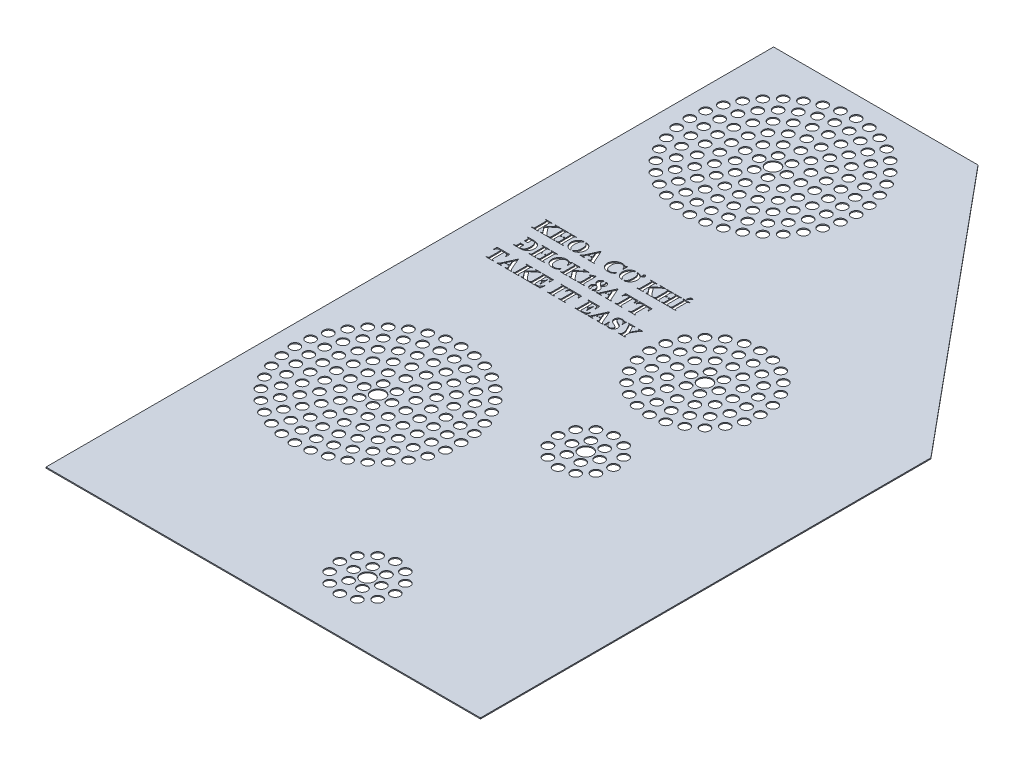
SolidWorks part; units mm, degrees
ref_plane "Front Plane" through (0, 0, 0) normal (0, 0, 1) x (1, 0, 0)
ref_plane "Top Plane" through (0, 0, 0) normal (0, 1, 0) x (1, 0, 0)
ref_plane "Right Plane" through (0, 0, 0) normal (1, 0, 0) x (0, 0, -1)
sketch "Sketch1" plane through (0, 0, 0) normal (0, 1, 0) x (1, 0, 0)
  line L0 (313.5, 0) -> (-313.5, 0)
  line L1 (-313.5, 0) -> (-313.5, 1050)
  line L2 (-313.5, 1050) -> (-18.5, 1050)
  line L3 (-18.5, 1050) -> (313.5, 650)
  line L4 (313.5, 650) -> (313.5, 0)
  line L5 (-263.5, 650) -> (-63.5, 650) construction
  circle A2 centre (-144.5, 330.2) radius 7
  circle A3 centre (-124.5, 330.2) radius 7
  circle A4 centre (-104.5, 330.2) radius 7
  circle A5 centre (-84.5, 330.2) radius 7
  circle A6 centre (-64.5, 330.2) radius 7
  circle A7 centre (-44.5, 330.2) radius 7
  circle A8 centre (-154.5, 312.8795) radius 7
  circle A9 centre (-174.5, 312.8795) radius 7
  circle A10 centre (-184.5, 330.2) radius 7
  circle A11 centre (-174.5, 347.5205) radius 7
  circle A12 centre (-154.5, 347.5205) radius 7
  circle A13 centre (-129.859, 310.2) radius 7
  circle A14 centre (-144.5, 295.559) radius 7
  circle A15 centre (-164.5, 290.2) radius 7
  circle A16 centre (-184.5, 295.559) radius 7
  circle A17 centre (-199.141, 310.2) radius 7
  circle A18 centre (-204.5, 330.2) radius 7
  circle A19 centre (-199.141, 350.2) radius 7
  circle A20 centre (-184.5, 364.841) radius 7
  circle A21 centre (-164.5, 370.2) radius 7
  circle A22 centre (-144.5, 364.841) radius 7
  circle A23 centre (-129.859, 350.2) radius 7
  circle A24 centre (-108.1184, 309.6788) radius 7
  circle A25 centre (-118.5373, 291.6327) radius 7
  circle A26 centre (-134.5, 278.2385) radius 7
  circle A27 centre (-154.0811, 271.1115) radius 7
  circle A28 centre (-174.9189, 271.1115) radius 7
  circle A29 centre (-194.5, 278.2385) radius 7
  circle A30 centre (-210.4627, 291.6327) radius 7
  circle A31 centre (-220.8816, 309.6788) radius 7
  circle A32 centre (-224.5, 330.2) radius 7
  circle A33 centre (-220.8816, 350.7212) radius 7
  circle A34 centre (-210.4627, 368.7673) radius 7
  circle A35 centre (-194.5, 382.1615) radius 7
  circle A36 centre (-174.9189, 389.2885) radius 7
  circle A37 centre (-154.0811, 389.2885) radius 7
  circle A38 centre (-134.5, 382.1615) radius 7
  circle A39 centre (-118.5373, 368.7673) radius 7
  circle A40 centre (-108.1184, 350.7212) radius 7
  circle A41 centre (-87.2259, 309.4945) radius 7
  circle A42 centre (-95.218, 290.2) radius 7
  circle A43 centre (-107.9315, 273.6315) radius 7
  circle A44 centre (-124.5, 260.918) radius 7
  circle A45 centre (-143.7945, 252.9259) radius 7
  circle A46 centre (-164.5, 250.2) radius 7
  circle A47 centre (-185.2055, 252.9259) radius 7
  circle A48 centre (-204.5, 260.918) radius 7
  circle A49 centre (-221.0685, 273.6315) radius 7
  circle A50 centre (-233.782, 290.2) radius 7
  circle A51 centre (-241.7741, 309.4945) radius 7
  circle A52 centre (-244.5, 330.2) radius 7
  circle A53 centre (-241.7741, 350.9055) radius 7
  circle A54 centre (-233.782, 370.2) radius 7
  circle A55 centre (-221.0685, 386.7685) radius 7
  circle A56 centre (-204.5, 399.482) radius 7
  circle A57 centre (-185.2055, 407.4741) radius 7
  circle A58 centre (-164.5, 410.2) radius 7
  circle A59 centre (-143.7945, 407.4741) radius 7
  circle A60 centre (-124.5, 399.482) radius 7
  circle A61 centre (-107.9315, 386.7685) radius 7
  circle A62 centre (-95.218, 370.2) radius 7
  circle A63 centre (-87.2259, 350.9055) radius 7
  circle A64 centre (-66.6852, 309.4088) radius 7
  circle A65 centre (-73.1455, 289.5263) radius 7
  circle A66 centre (-83.5983, 271.4215) radius 7
  circle A67 centre (-97.5869, 255.8855) radius 7
  circle A68 centre (-114.5, 243.5975) radius 7
  circle A69 centre (-133.5983, 235.0943) radius 7
  circle A70 centre (-154.0472, 230.7478) radius 7
  circle A71 centre (-174.9528, 230.7478) radius 7
  circle A72 centre (-195.4017, 235.0943) radius 7
  circle A73 centre (-214.5, 243.5975) radius 7
  circle A74 centre (-231.4131, 255.8855) radius 7
  circle A75 centre (-245.4017, 271.4215) radius 7
  circle A76 centre (-255.8545, 289.5263) radius 7
  circle A77 centre (-262.3148, 309.4088) radius 7
  circle A78 centre (-264.5, 330.2) radius 7
  circle A79 centre (-262.3148, 350.9912) radius 7
  circle A80 centre (-255.8545, 370.8737) radius 7
  circle A81 centre (-245.4017, 388.9785) radius 7
  circle A82 centre (-231.4131, 404.5145) radius 7
  circle A83 centre (-214.5, 416.8025) radius 7
  circle A84 centre (-195.4017, 425.3057) radius 7
  circle A85 centre (-174.9528, 429.6522) radius 7
  circle A86 centre (-154.0472, 429.6522) radius 7
  circle A87 centre (-133.5983, 425.3057) radius 7
  circle A88 centre (-114.5, 416.8025) radius 7
  circle A89 centre (-97.5869, 404.5145) radius 7
  circle A90 centre (-83.5983, 388.9785) radius 7
  circle A91 centre (-73.1455, 370.8737) radius 7
  circle A92 centre (-66.6852, 350.9912) radius 7
  circle A93 centre (-46.3231, 309.3622) radius 7
  circle A94 centre (-51.7369, 289.1576) radius 7
  circle A95 centre (-60.577, 270.2) radius 7
  circle A96 centre (-72.5747, 253.0655) radius 7
  circle A97 centre (-87.3655, 238.2747) radius 7
  circle A98 centre (-104.5, 226.277) radius 7
  circle A99 centre (-123.4576, 217.4369) radius 7
  circle A100 centre (-143.6622, 212.0231) radius 7
  circle A101 centre (-164.5, 210.2) radius 7
  circle A102 centre (-185.3378, 212.0231) radius 7
  circle A103 centre (-205.5424, 217.4369) radius 7
  circle A104 centre (-224.5, 226.277) radius 7
  circle A105 centre (-241.6345, 238.2747) radius 7
  circle A106 centre (-256.4253, 253.0655) radius 7
  circle A107 centre (-268.423, 270.2) radius 7
  circle A108 centre (-277.2631, 289.1576) radius 7
  circle A109 centre (-282.6769, 309.3622) radius 7
  circle A110 centre (-284.5, 330.2) radius 7
  circle A111 centre (-282.6769, 351.0378) radius 7
  circle A112 centre (-277.2631, 371.2424) radius 7
  circle A113 centre (-268.423, 390.2) radius 7
  circle A114 centre (-256.4253, 407.3345) radius 7
  circle A115 centre (-241.6345, 422.1253) radius 7
  circle A116 centre (-224.5, 434.123) radius 7
  circle A117 centre (-205.5424, 442.9631) radius 7
  circle A118 centre (-185.3378, 448.3769) radius 7
  circle A119 centre (-164.5, 450.2) radius 7
  circle A120 centre (-143.6622, 448.3769) radius 7
  circle A121 centre (-123.4576, 442.9631) radius 7
  circle A122 centre (-104.5, 434.123) radius 7
  circle A123 centre (-87.3655, 422.1253) radius 7
  circle A124 centre (-72.5747, 407.3345) radius 7
  circle A125 centre (-60.577, 390.2) radius 7
  circle A126 centre (-51.7369, 371.2424) radius 7
  circle A127 centre (-46.3231, 351.0378) radius 7
  circle A129 centre (-144.5, 900.2) radius 7
  circle A130 centre (-124.5, 900.2) radius 7
  circle A131 centre (-104.5, 900.2) radius 7
  circle A132 centre (-84.5, 900.2) radius 7
  circle A133 centre (-64.5, 900.2) radius 7
  circle A134 centre (-44.5, 900.2) radius 7
  circle A135 centre (-154.5, 882.8795) radius 7
  circle A136 centre (-174.5, 882.8795) radius 7
  circle A137 centre (-184.5, 900.2) radius 7
  circle A138 centre (-174.5, 917.5205) radius 7
  circle A139 centre (-154.5, 917.5205) radius 7
  circle A140 centre (-129.859, 880.2) radius 7
  circle A141 centre (-144.5, 865.559) radius 7
  circle A142 centre (-164.5, 860.2) radius 7
  circle A143 centre (-184.5, 865.559) radius 7
  circle A144 centre (-199.141, 880.2) radius 7
  circle A145 centre (-204.5, 900.2) radius 7
  circle A146 centre (-199.141, 920.2) radius 7
  circle A147 centre (-184.5, 934.841) radius 7
  circle A148 centre (-164.5, 940.2) radius 7
  circle A149 centre (-144.5, 934.841) radius 7
  circle A150 centre (-129.859, 920.2) radius 7
  circle A151 centre (-108.1184, 879.6788) radius 7
  circle A152 centre (-118.5373, 861.6327) radius 7
  circle A153 centre (-134.5, 848.2385) radius 7
  circle A154 centre (-154.0811, 841.1115) radius 7
  circle A155 centre (-174.9189, 841.1115) radius 7
  circle A156 centre (-194.5, 848.2385) radius 7
  circle A157 centre (-210.4627, 861.6327) radius 7
  circle A158 centre (-220.8816, 879.6788) radius 7
  circle A159 centre (-224.5, 900.2) radius 7
  circle A160 centre (-220.8816, 920.7212) radius 7
  circle A161 centre (-210.4627, 938.7673) radius 7
  circle A162 centre (-194.5, 952.1615) radius 7
  circle A163 centre (-174.9189, 959.2885) radius 7
  circle A164 centre (-154.0811, 959.2885) radius 7
  circle A165 centre (-134.5, 952.1615) radius 7
  circle A166 centre (-118.5373, 938.7673) radius 7
  circle A167 centre (-108.1184, 920.7212) radius 7
  circle A168 centre (-87.2259, 879.4945) radius 7
  circle A169 centre (-95.218, 860.2) radius 7
  circle A170 centre (-107.9315, 843.6315) radius 7
  circle A171 centre (-124.5, 830.918) radius 7
  circle A172 centre (-143.7945, 822.9259) radius 7
  circle A173 centre (-164.5, 820.2) radius 7
  circle A174 centre (-185.2055, 822.9259) radius 7
  circle A175 centre (-204.5, 830.918) radius 7
  circle A176 centre (-221.0685, 843.6315) radius 7
  circle A177 centre (-233.782, 860.2) radius 7
  circle A178 centre (-241.7741, 879.4945) radius 7
  circle A179 centre (-244.5, 900.2) radius 7
  circle A180 centre (-241.7741, 920.9055) radius 7
  circle A181 centre (-233.782, 940.2) radius 7
  circle A182 centre (-221.0685, 956.7685) radius 7
  circle A183 centre (-204.5, 969.482) radius 7
  circle A184 centre (-185.2055, 977.4741) radius 7
  circle A185 centre (-164.5, 980.2) radius 7
  circle A186 centre (-143.7945, 977.4741) radius 7
  circle A187 centre (-124.5, 969.482) radius 7
  circle A188 centre (-107.9315, 956.7685) radius 7
  circle A189 centre (-95.218, 940.2) radius 7
  circle A190 centre (-87.2259, 920.9055) radius 7
  circle A191 centre (-66.6852, 879.4088) radius 7
  circle A192 centre (-73.1455, 859.5263) radius 7
  circle A193 centre (-83.5983, 841.4215) radius 7
  circle A194 centre (-97.5869, 825.8855) radius 7
  circle A195 centre (-114.5, 813.5975) radius 7
  circle A196 centre (-133.5983, 805.0943) radius 7
  circle A197 centre (-154.0472, 800.7478) radius 7
  circle A198 centre (-174.9528, 800.7478) radius 7
  circle A199 centre (-195.4017, 805.0943) radius 7
  circle A200 centre (-214.5, 813.5975) radius 7
  circle A201 centre (-231.4131, 825.8855) radius 7
  circle A202 centre (-245.4017, 841.4215) radius 7
  circle A203 centre (-255.8545, 859.5263) radius 7
  circle A204 centre (-262.3148, 879.4088) radius 7
  circle A205 centre (-264.5, 900.2) radius 7
  circle A206 centre (-262.3148, 920.9912) radius 7
  circle A207 centre (-255.8545, 940.8737) radius 7
  circle A208 centre (-245.4017, 958.9785) radius 7
  circle A209 centre (-231.4131, 974.5145) radius 7
  circle A210 centre (-214.5, 986.8025) radius 7
  circle A211 centre (-195.4017, 995.3057) radius 7
  circle A212 centre (-174.9528, 999.6522) radius 7
  circle A213 centre (-154.0472, 999.6522) radius 7
  circle A214 centre (-133.5983, 995.3057) radius 7
  circle A215 centre (-114.5, 986.8025) radius 7
  circle A216 centre (-97.5869, 974.5145) radius 7
  circle A217 centre (-83.5983, 958.9785) radius 7
  circle A218 centre (-73.1455, 940.8737) radius 7
  circle A219 centre (-66.6852, 920.9912) radius 7
  circle A220 centre (-46.3231, 879.3622) radius 7
  circle A221 centre (-51.7369, 859.1576) radius 7
  circle A222 centre (-60.577, 840.2) radius 7
  circle A223 centre (-72.5747, 823.0655) radius 7
  circle A224 centre (-87.3655, 808.2747) radius 7
  circle A225 centre (-104.5, 796.277) radius 7
  circle A226 centre (-123.4576, 787.4369) radius 7
  circle A227 centre (-143.6622, 782.0231) radius 7
  circle A228 centre (-164.5, 780.2) radius 7
  circle A229 centre (-185.3378, 782.0231) radius 7
  circle A230 centre (-205.5424, 787.4369) radius 7
  circle A231 centre (-224.5, 796.277) radius 7
  circle A232 centre (-241.6345, 808.2747) radius 7
  circle A233 centre (-256.4253, 823.0655) radius 7
  circle A234 centre (-268.423, 840.2) radius 7
  circle A235 centre (-277.2631, 859.1576) radius 7
  circle A236 centre (-282.6769, 879.3622) radius 7
  circle A237 centre (-284.5, 900.2) radius 7
  circle A238 centre (-282.6769, 921.0378) radius 7
  circle A239 centre (-277.2631, 941.2424) radius 7
  circle A240 centre (-268.423, 960.2) radius 7
  circle A241 centre (-256.4253, 977.3345) radius 7
  circle A242 centre (-241.6345, 992.1253) radius 7
  circle A243 centre (-224.5, 1004.123) radius 7
  circle A244 centre (-205.5424, 1012.9631) radius 7
  circle A245 centre (-185.3378, 1018.3769) radius 7
  circle A246 centre (-164.5, 1020.2) radius 7
  circle A247 centre (-143.6622, 1018.3769) radius 7
  circle A248 centre (-123.4576, 1012.9631) radius 7
  circle A249 centre (-104.5, 1004.123) radius 7
  circle A250 centre (-87.3655, 992.1253) radius 7
  circle A251 centre (-72.5747, 977.3345) radius 7
  circle A252 centre (-60.577, 960.2) radius 7
  circle A253 centre (-51.7369, 941.2424) radius 7
  circle A254 centre (-46.3231, 921.0378) radius 7
  circle A256 centre (-164.5, 330.2) radius 10
  circle A257 centre (-164.5, 900.2) radius 10
  circle A259 centre (76.5, 581) radius 7
  circle A260 centre (96.5, 581) radius 7
  circle A261 centre (116.5, 581) radius 7
  circle A262 centre (136.5, 581) radius 7
  circle A263 centre (56.5, 581) radius 10
  circle A264 centre (66.5, 563.6795) radius 7
  circle A265 centre (46.5, 563.6795) radius 7
  circle A266 centre (36.5, 581) radius 7
  circle A267 centre (46.5, 598.3205) radius 7
  circle A268 centre (66.5, 598.3205) radius 7
  circle A269 centre (91.141, 561) radius 7
  circle A270 centre (76.5, 546.359) radius 7
  circle A271 centre (56.5, 541) radius 7
  circle A272 centre (36.5, 546.359) radius 7
  circle A273 centre (21.859, 561) radius 7
  circle A274 centre (16.5, 581) radius 7
  circle A275 centre (21.859, 601) radius 7
  circle A276 centre (36.5, 615.641) radius 7
  circle A277 centre (56.5, 621) radius 7
  circle A278 centre (76.5, 615.641) radius 7
  circle A279 centre (91.141, 601) radius 7
  circle A280 centre (112.8816, 560.4788) radius 7
  circle A281 centre (102.4627, 542.4327) radius 7
  circle A282 centre (86.5, 529.0385) radius 7
  circle A283 centre (66.9189, 521.9115) radius 7
  circle A284 centre (46.0811, 521.9115) radius 7
  circle A285 centre (26.5, 529.0385) radius 7
  circle A286 centre (10.5373, 542.4327) radius 7
  circle A287 centre (0.1184, 560.4788) radius 7
  circle A288 centre (-3.5, 581) radius 7
  circle A289 centre (0.1184, 601.5212) radius 7
  circle A290 centre (10.5373, 619.5673) radius 7
  circle A291 centre (26.5, 632.9615) radius 7
  circle A292 centre (46.0811, 640.0885) radius 7
  circle A293 centre (66.9189, 640.0885) radius 7
  circle A294 centre (86.5, 632.9615) radius 7
  circle A295 centre (102.4627, 619.5673) radius 7
  circle A296 centre (112.8816, 601.5212) radius 7
  circle A297 centre (133.7741, 560.2945) radius 7
  circle A298 centre (125.782, 541) radius 7
  circle A299 centre (113.0685, 524.4315) radius 7
  circle A300 centre (96.5, 511.718) radius 7
  circle A301 centre (77.2055, 503.7259) radius 7
  circle A302 centre (56.5, 501) radius 7
  circle A303 centre (35.7945, 503.7259) radius 7
  circle A304 centre (16.5, 511.718) radius 7
  circle A305 centre (-0.0685, 524.4315) radius 7
  circle A306 centre (-12.782, 541) radius 7
  circle A307 centre (-20.7741, 560.2945) radius 7
  circle A308 centre (-23.5, 581) radius 7
  circle A309 centre (-20.7741, 601.7055) radius 7
  circle A310 centre (-12.782, 621) radius 7
  circle A311 centre (-0.0685, 637.5685) radius 7
  circle A312 centre (16.5, 650.282) radius 7
  circle A313 centre (35.7945, 658.2741) radius 7
  circle A314 centre (56.5, 661) radius 7
  circle A315 centre (77.2055, 658.2741) radius 7
  circle A316 centre (96.5, 650.282) radius 7
  circle A317 centre (113.0685, 637.5685) radius 7
  circle A318 centre (125.782, 621) radius 7
  circle A319 centre (133.7741, 601.7055) radius 7
  circle A362 centre (76.5, 409) radius 7
  circle A363 centre (96.5, 409) radius 7
  circle A364 centre (66.5, 391.6795) radius 7
  circle A365 centre (46.5, 391.6795) radius 7
  circle A366 centre (36.5, 409) radius 7
  circle A367 centre (46.5, 426.3205) radius 7
  circle A368 centre (66.5, 426.3205) radius 7
  circle A369 centre (91.141, 389) radius 7
  circle A370 centre (76.5, 374.359) radius 7
  circle A371 centre (56.5, 369) radius 7
  circle A372 centre (36.5, 374.359) radius 7
  circle A373 centre (21.859, 389) radius 7
  circle A374 centre (16.5, 409) radius 7
  circle A375 centre (21.859, 429) radius 7
  circle A376 centre (36.5, 443.641) radius 7
  circle A377 centre (56.5, 449) radius 7
  circle A378 centre (76.5, 443.641) radius 7
  circle A379 centre (91.141, 429) radius 7
  circle A380 centre (56.5, 409) radius 10
  circle A381 centre (76.5, 94) radius 7
  circle A382 centre (96.5, 94) radius 7
  circle A383 centre (66.5, 76.6795) radius 7
  circle A384 centre (46.5, 76.6795) radius 7
  circle A385 centre (36.5, 94) radius 7
  circle A386 centre (46.5, 111.3205) radius 7
  circle A387 centre (66.5, 111.3205) radius 7
  circle A388 centre (91.141, 74) radius 7
  circle A389 centre (76.5, 59.359) radius 7
  circle A390 centre (56.5, 54) radius 7
  circle A391 centre (36.5, 59.359) radius 7
  circle A392 centre (21.859, 74) radius 7
  circle A393 centre (16.5, 94) radius 7
  circle A394 centre (21.859, 114) radius 7
  circle A395 centre (36.5, 128.641) radius 7
  circle A396 centre (56.5, 134) radius 7
  circle A397 centre (76.5, 128.641) radius 7
  circle A398 centre (91.141, 114) radius 7
  circle A399 centre (56.5, 94) radius 10
  text T0 "<b>KHOA CƠ KHÍ</b>\r\n<b>DHCK18ATT</b>\r\n<b>TAKE IT EASY</b>" font "Times New Roman" height 20
  point P35 (-164.5, 330.2)
  point P58 (-164.5, 330.2)
  point P93 (-164.5, 330.2)
  point P139 (-164.5, 330.2)
  point P199 (-164.5, 330.2)
  point P270 (-164.5, 330.2)
  point P294 (-164.5, 900.2)
  point P317 (-164.5, 900.2)
  point P352 (-164.5, 900.2)
  point P398 (-164.5, 900.2)
  point P457 (-164.5, 900.2)
  point P528 (-164.5, 900.2)
  point P550 (56.5, 581)
  point P574 (56.5, 581)
  point P609 (56.5, 581)
  point P656 (56.5, 581)
  point P672 (56.5, 409)
  point P695 (56.5, 409)
  point P710 (56.5, 94)
  point P733 (56.5, 94)
  dimension "D5" = 2
  dimension "D6" = 20
  dimension "D7" = 2
  dimension "D8" = 20
  dimension "D16" = 172
  dimension "D9" = 20
  dimension "D17" = 20
  dimension "D18" = 6
  dimension "D1" = 650
  dimension "D2" = 1050
  dimension "D3" = 627
  dimension "D4" = 295
  dimension "D24" = 370
  dimension "D25" = 469
  dimension "D22" = 200
  dimension "D23" = 50
  dimension "D26" = 400
  dimension "D10" = 6
  dimension "D11" = 12
  dimension "D12" = 18
  dimension "D13" = 24
  dimension "D14" = 30
  dimension "D15" = 36
  dimension "D19" = 12
  dimension "D20" = 18
  dimension "D21" = 24
extrude "Boss-Extrude1" add sketch "Sketch1" along normal blind 1.5
sketch "Sketch2" plane through (0, 1.5, 0) normal (0, 1, 0) x (1, 0, 0)
  line L1 (-227.3073, 658.93) -> (-229.6927, 658.93)
  line L2 (-227.3073, 658.93) -> (-227.3073, 661.988)
  line L3 (-227.3073, 661.988) -> (-229.6927, 661.988)
  line L4 (-229.6927, 658.93) -> (-229.6927, 661.988)
  line L5 (-227.3073, 658.93) -> (-229.6927, 661.988) construction
  line L6 (-227.3073, 661.988) -> (-229.6927, 658.93) construction
  line L7 (-203.7646, 667.9852) -> (-206.7139, 667.9852)
  line L8 (-203.7646, 667.9852) -> (-203.7646, 671.1874)
  line L9 (-203.7646, 671.1874) -> (-206.7139, 671.1874)
  line L10 (-206.7139, 667.9852) -> (-206.7139, 671.1874)
  line L11 (-203.7646, 667.9852) -> (-206.7139, 671.1874) construction
  line L12 (-203.7646, 671.1874) -> (-206.7139, 667.9852) construction
  line L13 (-203.7646, 648.6458) -> (-206.7139, 648.6458)
  line L14 (-203.7646, 648.6458) -> (-203.7646, 652.0165)
  line L15 (-203.7646, 652.0165) -> (-206.7139, 652.0165)
  line L16 (-206.7139, 648.6458) -> (-206.7139, 652.0165)
  line L17 (-203.7646, 648.6458) -> (-206.7139, 652.0165) construction
  line L18 (-203.7646, 652.0165) -> (-206.7139, 648.6458) construction
  line L19 (-183.2916, 655.0807) -> (-185.2189, 655.0807)
  line L20 (-183.2916, 655.0807) -> (-183.2916, 657.4898)
  line L21 (-183.2916, 657.4898) -> (-185.2189, 657.4898)
  line L22 (-185.2189, 655.0807) -> (-185.2189, 657.4898)
  line L23 (-183.2916, 655.0807) -> (-185.2189, 657.4898) construction
  line L24 (-183.2916, 657.4898) -> (-185.2189, 655.0807) construction
  line L25 (-129.4086, 667.9852) -> (-132.6017, 667.9852)
  line L26 (-129.4086, 667.9852) -> (-129.4086, 671.1874)
  line L27 (-129.4086, 671.1874) -> (-132.6017, 671.1874)
  line L28 (-132.6017, 667.9852) -> (-132.6017, 671.1874)
  line L29 (-129.4086, 667.9852) -> (-132.6017, 671.1874) construction
  line L30 (-129.4086, 671.1874) -> (-132.6017, 667.9852) construction
  line L31 (-129.4086, 648.6458) -> (-132.6017, 648.6458)
  line L32 (-129.4086, 648.6458) -> (-129.4086, 652.0165)
  line L33 (-129.4086, 652.0165) -> (-132.6017, 652.0165)
  line L34 (-132.6017, 648.6458) -> (-132.6017, 652.0165)
  line L35 (-129.4086, 648.6458) -> (-132.6017, 652.0165) construction
  line L36 (-129.4086, 652.0165) -> (-132.6017, 648.6458) construction
  line L37 (-75.661, 658.93) -> (-78.0057, 658.93)
  line L38 (-75.661, 658.93) -> (-75.661, 661.988)
  line L39 (-75.661, 661.988) -> (-78.0057, 661.988)
  line L40 (-78.0057, 658.93) -> (-78.0057, 661.988)
  line L41 (-75.661, 658.93) -> (-78.0057, 661.988) construction
  line L42 (-75.661, 661.988) -> (-78.0057, 658.93) construction
  line L43 (-244.2793, 622.3115) -> (-253.7001, 622.3115)
  line L44 (-244.2793, 622.3115) -> (-244.2793, 627.9107)
  line L45 (-244.2793, 627.9107) -> (-253.7001, 627.9107)
  line L46 (-253.7001, 622.3115) -> (-253.7001, 627.9107)
  line L47 (-244.2793, 622.3115) -> (-253.7001, 627.9107) construction
  line L48 (-244.2793, 627.9107) -> (-253.7001, 622.3115) construction
  line L49 (-219.2306, 623.9207) -> (-222.7694, 623.9207)
  line L50 (-219.2306, 623.9207) -> (-219.2306, 627.4482)
  line L51 (-219.2306, 627.4482) -> (-222.7694, 627.4482)
  line L52 (-222.7694, 623.9207) -> (-222.7694, 627.4482)
  line L53 (-219.2306, 623.9207) -> (-222.7694, 627.4482) construction
  line L54 (-219.2306, 627.4482) -> (-222.7694, 623.9207) construction
  line L55 (-140.1148, 632.969) -> (-143.1266, 632.969)
  line L56 (-140.1148, 632.969) -> (-140.1148, 636.7397)
  line L57 (-140.1148, 636.7397) -> (-143.1266, 636.7397)
  line L58 (-143.1266, 632.969) -> (-143.1266, 636.7397)
  line L59 (-140.1148, 632.969) -> (-143.1266, 636.7397) construction
  line L60 (-140.1148, 636.7397) -> (-143.1266, 632.969) construction
  line L61 (-140.5431, 613.7711) -> (-143.6792, 613.7711)
  line L62 (-140.5431, 613.7711) -> (-140.5431, 617.4235)
  line L63 (-140.5431, 617.4235) -> (-143.6792, 617.4235)
  line L64 (-143.6792, 613.7711) -> (-143.6792, 617.4235)
  line L65 (-140.5431, 613.7711) -> (-143.6792, 617.4235) construction
  line L66 (-140.5431, 617.4235) -> (-143.6792, 613.7711) construction
  line L67 (-123.8878, 619.9311) -> (-126.2893, 619.9311)
  line L68 (-123.8878, 619.9311) -> (-123.8878, 622.8798)
  line L69 (-123.8878, 622.8798) -> (-126.2893, 622.8798)
  line L70 (-126.2893, 619.9311) -> (-126.2893, 622.8798)
  line L71 (-123.8878, 619.9311) -> (-126.2893, 622.8798) construction
  line L72 (-123.8878, 622.8798) -> (-126.2893, 619.9311) construction
  line L73 (-233.1289, 584.954) -> (-235.3815, 584.954)
  line L74 (-233.1289, 584.954) -> (-233.1289, 588.0837)
  line L75 (-233.1289, 588.0837) -> (-235.3815, 588.0837)
  line L76 (-235.3815, 584.954) -> (-235.3815, 588.0837)
  line L77 (-233.1289, 584.954) -> (-235.3815, 588.0837) construction
  line L78 (-233.1289, 588.0837) -> (-235.3815, 584.954) construction
  line L79 (-101.6547, 585.1955) -> (-103.5224, 585.1955)
  line L80 (-101.6547, 585.1955) -> (-101.6547, 587.8421)
  line L81 (-101.6547, 587.8421) -> (-103.5224, 587.8421)
  line L82 (-103.5224, 585.1955) -> (-103.5224, 587.8421)
  line L83 (-101.6547, 585.1955) -> (-103.5224, 587.8421) construction
  line L84 (-101.6547, 587.8421) -> (-103.5224, 585.1955) construction
  point P0 (-228.5, 660.459)
  point P5 (-205.2393, 669.5863)
  point P10 (-205.2393, 650.3311)
  point P15 (-184.2552, 656.2852)
  point P20 (-131.0051, 669.5863)
  point P25 (-131.0051, 650.3311)
  point P30 (-76.8333, 660.459)
  point P35 (-248.9897, 625.1111)
  point P40 (-221, 625.6845)
  point P45 (-141.6207, 634.8544)
  point P50 (-142.1111, 615.5973)
  point P55 (-125.0885, 621.4055)
  point P60 (-234.2552, 586.5188)
  point P65 (-102.5885, 586.5188)
extrude "Boss-Extrude2" add sketch "Sketch2" against normal blind 1.5
